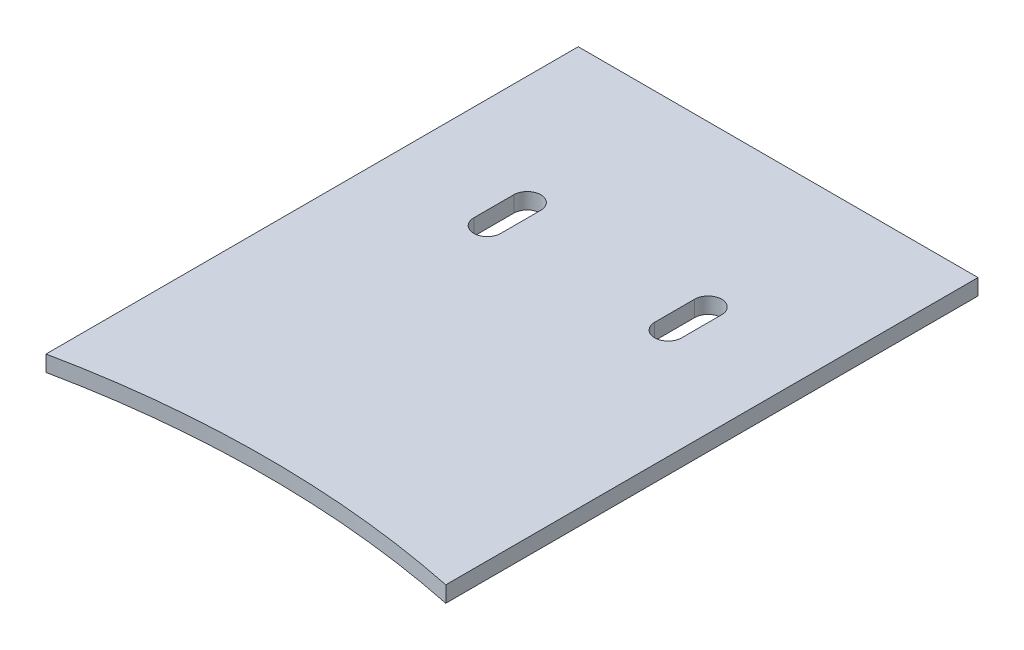
SolidWorks part; units mm, degrees
material "普通碳钢"
ref_plane "前视基准面" through (0, 0, 0) normal (0, 0, 1) x (1, 0, 0)
ref_plane "上视基准面" through (0, 0, 0) normal (0, 1, 0) x (1, 0, 0)
ref_plane "右视基准面" through (0, 0, 0) normal (1, 0, 0) x (0, 0, -1)
sketch "草图1" plane through (0, 0, 0) normal (0, 1, 0) x (1, 0, 0)
  line L0 (0, 0) -> (0, 1497.5) construction
  line L1 (-200, 1497.5) -> (200, 1497.5) construction
  line L2 (200, 1497.5) -> (200, 964.9924) construction
  line L3 (-200, 1497.5) -> (-200, 964.9924) construction
  line L4 (-200, 964.9924) -> (-200, 1497.5)
  line L5 (-200, 1497.5) -> (200, 1497.5)
  line L6 (200, 1497.5) -> (200, 964.9924)
  line L7 (-90.5, 1337) -> (-90.5, 1297) construction
  line L8 (-77, 1337) -> (-77, 1297)
  line L9 (-104, 1337) -> (-104, 1297)
  line L10 (90.5, 1297) -> (90.5, 1337) construction
  line L11 (77, 1297) -> (77, 1337)
  line L12 (104, 1297) -> (104, 1337)
  line L13 (-90.5, 1317) -> (90.5, 1317) construction
  circle A0 centre (0, 0) radius 985.5 construction
  arc A1 (-200, 964.9924) -> (200, 964.9924) centre (0, 0) cw
  arc A2 (-77, 1337) -> (-104, 1337) centre (-90.5, 1337) ccw
  arc A3 (-104, 1297) -> (-77, 1297) centre (-90.5, 1297) ccw
  arc A4 (77, 1297) -> (104, 1297) centre (90.5, 1297) ccw
  arc A5 (104, 1337) -> (77, 1337) centre (90.5, 1337) ccw
  point P5 (0, 0)
  point P12 (-90.5, 1317)
  point P18 (90.5, 1317)
  dimension "D1" = 1971
  dimension "D2" = 1497.5
  dimension "D3" = 400
  dimension "D4" = 200
  dimension "D5" = 27
  dimension "D6" = 40
  dimension "D7" = 181
  dimension "D8" = 1317
  dimension "D9" = 180.5
base flange "基体-法兰1" sketch "草图1" thickness 16 reverse thickness direction yes parameters "D1"=10
sketch "草图6" plane through (0, 16, 0) normal (0, 1, 0) x (1, 0, 0)
  line L0 (200, 1497.5) -> (-200, 1497.5) construction
  line L1 (-200, 1497.5) -> (200, 1497.5)
  line L2 (-200, 1497.5) -> (-200, 964.9924)
  line L3 (-200, 964.9924) -> (200, 964.9924)
  line L4 (200, 1497.5) -> (200, 964.9924)
  line L5 (-200, 1497.5) -> (-200, 964.9924) construction
  line L6 (200, 964.9924) -> (200, 1497.5) construction
  dimension "D1" = 400
  dimension "D2" = 532.5076
sketch "折弯-线1" plane through (0, 0, 0) normal (0, 1, 0) x (1, 0, 0)
sketch "边界框1" plane through (0, 0, 0) normal (0, 1, 0) x (1, 0, 0)
sheet metal parameters "钣金1" thickness 16 parameters "D1"=10
flat pattern "平板型式1" [suppressed]
sketch "折弯-线2" plane through (0, 0, 0) normal (0, 1, 0) x (1, 0, 0)
sketch "边界框2" [suppressed] plane through (0, 0, 0) normal (0, 1, 0) x (1, 0, 0)
